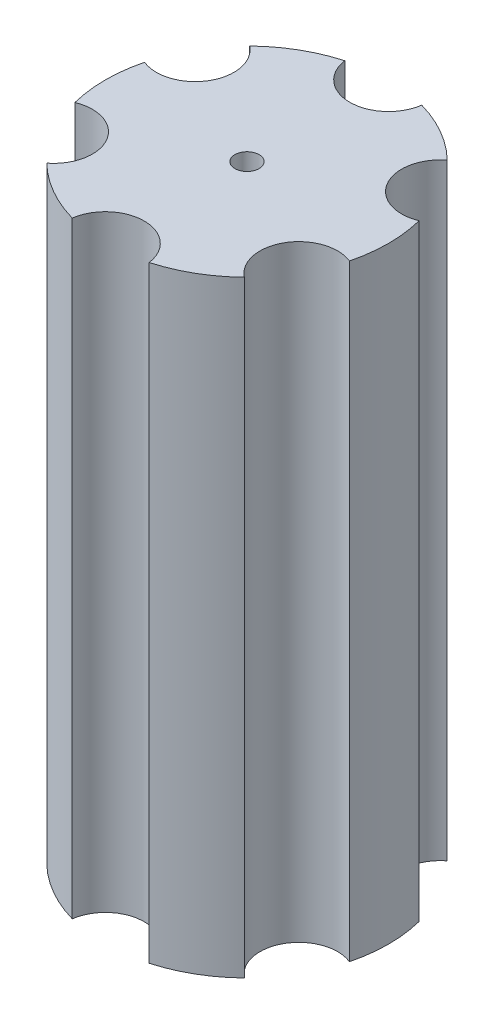
SolidWorks part; units mm, degrees
ref_plane "Front Plane" through (0, 0, 0) normal (0, 0, 1) x (1, 0, 0)
ref_plane "Top Plane" through (0, 0, 0) normal (0, 1, 0) x (1, 0, 0)
ref_plane "Right Plane" through (0, 0, 0) normal (1, 0, 0) x (0, 0, -1)
sketch "Sketch1" plane through (0, 0, 0) normal (0, 1, 0) x (1, 0, 0)
  arc A0 (-4.7546, 16.8417) -> (4.7546, 16.8417) centre (0, 17.5) ccw
  arc A1 (12.208, 12.5385) -> (16.9627, 4.3032) centre (15.1554, 8.75) ccw
  arc A2 (16.9627, -4.3032) -> (12.208, -12.5385) centre (15.1554, -8.75) ccw
  arc A3 (4.7546, -16.8417) -> (-4.7546, -16.8417) centre (0, -17.5) ccw
  arc A4 (-12.208, -12.5385) -> (-16.9627, -4.3032) centre (-15.1554, -8.75) ccw
  arc A5 (-16.9627, 4.3032) -> (-12.208, 12.5385) centre (-15.1554, 8.75) ccw
  arc A6 (-16.9627, 4.3032) -> (-16.9627, -4.3032) centre (0, 0) ccw
  arc A7 (-12.208, -12.5385) -> (-4.7546, -16.8417) centre (0, 0) ccw
  arc A8 (-12.208, -12.5385) -> (-4.7546, -16.8417) centre (0, 0) ccw construction
  arc A9 (4.7546, -16.8417) -> (12.208, -12.5385) centre (0, 0) ccw
  arc A10 (4.7546, -16.8417) -> (12.208, -12.5385) centre (0, 0) ccw construction
  arc A11 (16.9627, -4.3032) -> (16.9627, 4.3032) centre (0, 0) ccw
  circle A12 centre (0, 0) radius 1.5
  arc A13 (-16.9627, 4.3032) -> (-16.9627, -4.3032) centre (0, 0) ccw construction
  arc A14 (16.9627, -4.3032) -> (16.9627, 4.3032) centre (0, 0) ccw construction
  arc A15 (12.208, 12.5385) -> (4.7546, 16.8417) centre (0, 0) ccw
  arc A16 (12.208, 12.5385) -> (4.7546, 16.8417) centre (0, 0) ccw construction
  arc A17 (-4.7546, 16.8417) -> (-12.208, 12.5385) centre (0, 0) ccw
  arc A18 (-4.7546, 16.8417) -> (-12.208, 12.5385) centre (0, 0) ccw construction
  point P6 (0, 0)
  point P18 (0, 0)
  point P19 (-1.1857, 0.8067)
  point P20 (0, 0)
  point P21 (-14.3197, 4.6278)
  point P22 (0, 0)
  point P23 (-13.548, -7.8219)
  dimension "D2" = 6
  dimension "D3" = 35
  dimension "D4" = 3
  dimension "D1" = 9.6
extrude "Boss-Extrude1" add sketch "Sketch1" along normal blind 75
